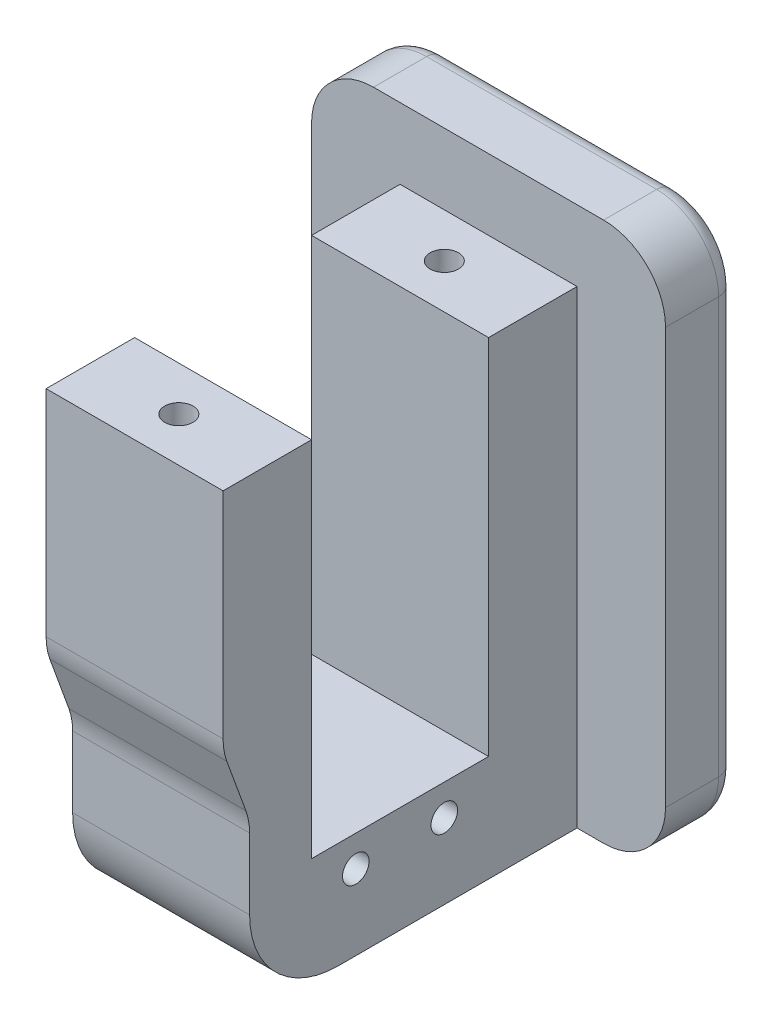
SolidWorks part; units mm, degrees
ref_plane "Front Plane" through (0, 0, 0) normal (0, 0, 1) x (1, 0, 0)
ref_plane "Top Plane" through (0, 0, 0) normal (0, 1, 0) x (1, 0, 0)
ref_plane "Right Plane" through (0, 0, 0) normal (1, 0, 0) x (0, 0, -1)
sketch "Sketch3" plane through (0, 0, 30) normal (0, 0, -1) x (-1, 0, 0)
  line L0 (95, 33.2573) -> (65, 33.2573) construction
  line L15 (80, 53.2573) -> (80, 33.2573) construction
  line L20 (55, 53.2573) -> (105, 53.2573)
  line L29 (55, -26.7427) -> (105, -26.7427)
  line L31 (110, -21.7427) -> (110, 48.2573)
  line L33 (50, -21.7427) -> (50, 48.2573)
  arc A17 (50, 48.2573) -> (55, 53.2573) centre (55, 48.2573) cw
  arc A18 (110, 48.2573) -> (105, 53.2573) centre (105, 48.2573) ccw
  arc A21 (50, -21.7427) -> (55, -26.7427) centre (55, -21.7427) ccw
  arc A22 (110, -21.7427) -> (105, -26.7427) centre (105, -21.7427) cw
  dimension "D1" = 5
extrude "Boss-Extrude1" add sketch "Sketch3" along normal blind 8
ref_plane "Plane1" through (-80, 0, 0) normal (-1, 0, 0) x (0, 0, 1)
sketch "Sketch8" plane through (0, 0, 22) normal (0, 0, -1) x (-1, 0, 0)
  line L0 (50, 13.2573) -> (110, 13.2573) construction
  line L1 (50, 48.2573) -> (50, -21.7427) construction
  line L2 (110, -21.7427) -> (110, 48.2573) construction
  line L3 (80, 13.2573) -> (80, -26.7427) construction
  line L4 (55, -26.7427) -> (105, -26.7427) construction
  line L5 (78.25, 15.3786) -> (78.25, 11.136)
  line L6 (81.75, 15.3786) -> (81.75, 11.136)
  arc A0 (78.25, 11.136) -> (81.75, 11.136) centre (80, 13.2573) ccw
  arc A1 (81.75, 15.3786) -> (78.25, 15.3786) centre (80, 13.2573) ccw
extrude "Cut-Extrude3" cut sketch "Sketch8" against normal blind 3
sketch "Sketch10" plane through (0, 0, 22) normal (0, 0, -1) x (-1, 0, 0)
  line L0 (50, 13.2573) -> (110, 13.2573) construction
  line L1 (50, 48.2573) -> (50, -21.7427) construction
  line L2 (110, -21.7427) -> (110, 48.2573) construction
  line L3 (80, 13.2573) -> (80, -26.7427) construction
  line L4 (55, -26.7427) -> (105, -26.7427) construction
  line L7 (81.75, 11.136) -> (81.75, 15.3786)
  line L8 (78.25, 15.3786) -> (78.25, 11.136)
  line L9 (81.75, 11.136) -> (81.75, 15.3786)
  line L10 (78.25, 15.3786) -> (78.25, 11.136)
  circle A3 centre (80, 13.2573) radius 9.75
  arc A5 (78.25, 11.136) -> (81.75, 11.136) centre (80, 13.2573) ccw
  arc A6 (81.75, 15.3786) -> (78.25, 15.3786) centre (80, 13.2573) ccw
  arc A7 (78.25, 11.136) -> (81.75, 11.136) centre (80, 13.2573) ccw
  arc A8 (81.75, 15.3786) -> (78.25, 15.3786) centre (80, 13.2573) ccw
  dimension "D1" = 0
extrude "Boss-Extrude4" add sketch "Sketch10" along normal blind 9
sketch "Sketch12" plane through (-80, 0, 0) normal (-1, 0, 0) x (0, 0, 1)
  line L0 (30, -19.2427) -> (30, 33.7573)
  line L2 (30, -21.7427) -> (30, 48.2573) construction
  line L21 (40, 33.7573) -> (40, -7.2427)
  line L22 (40, -7.2427) -> (60, -7.2427)
  line L24 (67.0011, -19.2427) -> (30, -19.2427)
  line L25 (40, 0.0073) -> (40, 26.5073) construction
  line L27 (60, -6.9927) -> (40, -6.9927) construction
  line L35 (60, 39.4573) -> (60, 33.5073) construction
  line L36 (60, 33.7573) -> (60, -7.2427)
  line L40 (60, 33.7573) -> (70, 33.7573)
  line L41 (40, 33.7573) -> (30, 33.7573)
  line L42 (70, 33.7573) -> (70, 8.2394)
  line L43 (70, 8.2394) -> (67.0011, 0)
  line L44 (67.0011, 0) -> (67.0011, -19.2427)
  dimension "D1" = 0
  dimension "D2" = 10
  dimension "D3" = 0.25
  dimension "D4" = 160
extrude "Boss-Extrude5" add sketch "Sketch12" along normal mid plane 20
sketch "Sketch13" plane through (-70, 0, 0) normal (1, 0, 0) x (0, 0, -1)
  circle A0 centre (-55, -10.7427) radius 1.5
  circle A1 centre (-45, -10.7427) radius 1.5
  circle A2 centre (-55, 37.2573) radius 1.5
  circle A3 centre (-45, 37.2573) radius 1.5
extrude "Cut-Extrude4" cut sketch "Sketch13" against normal blind 10
sketch "Sketch14" plane through (0, 0, 22) normal (0, 0, -1) x (-1, 0, 0)
  circle A0 centre (80, 13.2573) radius 12
extrude "Boss-Extrude6" add sketch "Sketch14" along normal blind 1
fillet "Fillet4" radius 10 1 edges at (-80, -19.2427, 67.0011)
fillet "Fillet5" radius 7 2 edges at (-80, 8.2394, 70) (-80, 0, 67.0011)
sketch "Sketch15" plane through (0, 0, 30) normal (0, 0, 1) x (1, 0, 0)
  line L1 (-100, -19.2427) -> (-60, -19.2427)
  line L3 (-100, 41.7573) -> (-60, 41.7573)
  line L7 (-60, 41.7573) -> (-60, -19.2427)
  line L8 (-80, 33.7573) -> (-80, 14.8628) construction
  line L9 (-90, 33.7573) -> (-70, 33.7573) construction
  line L10 (-100, 41.7573) -> (-100, -19.2427)
  point P2 (0, 0)
  point P3 (-99.1952, 41.7573)
  point P4 (-99.1952, -19.2427)
  dimension "D1" = 20
  dimension "D2" = 20
extrude "Cut-Extrude5" cut sketch "Sketch15" against normal through all flip side to cut
fillet "Fillet6" radius 7 4 edges at (-60, -19.2427, 26) (-100, -19.2427, 26) (-100, 41.7573, 26) (-60, 41.7573, 26)
sketch "Sketch16" plane through (0, 33.7573, 0) normal (0, 1, 0) x (1, 0, 0)
  circle A0 centre (-80, -65) radius 1.6
  circle A1 centre (-80, -35) radius 1.6
extrude "Cut-Extrude6" cut sketch "Sketch16" against normal blind 15
fillet "Fillet7" radius 2 8 edges at (-62.0503, 39.707, 22) (-80, 41.7573, 22) (-97.9497, 39.707, 22) (-100, 11.2573, 22) (-97.9497, -17.1925, 22) (-80, -19.2427, 22) (-62.0503, -17.1925, 22) (-60, 11.2573, 22)
